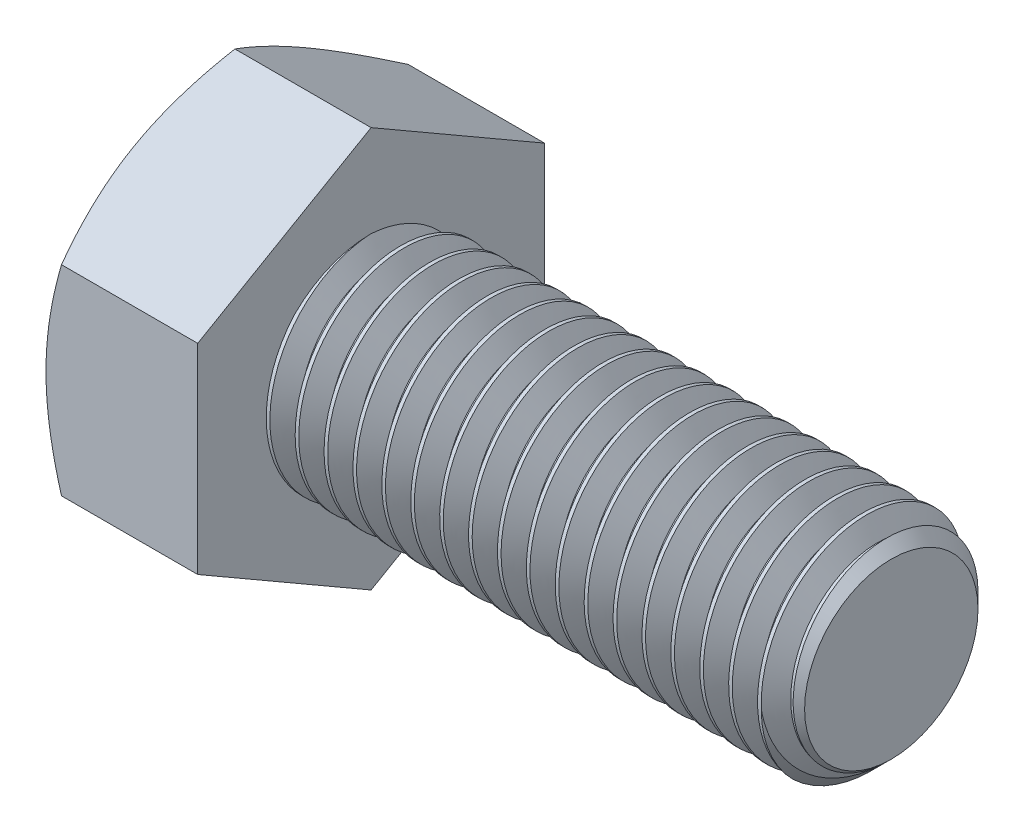
SolidWorks part; units mm, degrees
ref_plane "Front Plane" through (0, 0, 0) normal (0, 0, 1) x (1, 0, 0)
ref_plane "Top Plane" through (0, 0, 0) normal (0, 1, 0) x (1, 0, 0)
ref_plane "Right Plane" through (0, 0, 0) normal (1, 0, 0) x (0, 0, -1)
sketch "Sketch1" plane through (0, 0, 0) normal (0, 0, 1) x (1, 0, 0)
  line L0 (-12.3031, 0) -> (12.3031, 0) construction
  line L1 (12.3031, 3.9688) -> (12.3031, -3.9688) construction
  line L2 (-6.7469, 6.35) -> (-6.7469, -6.35) construction
  line L3 (-12.3031, 6.35) -> (-12.3031, -6.35) construction
  point P9 (-6.7469, 0)
  point P10 (8.599, -3.9688)
  dimension "D1" = 3.7042
  dimension "Screw Dia" = 7.9375
  dimension "Hex" = 12.7
  dimension "Head Ht" = 5.5562
  dimension "Screw Lenght" = 19.05
ref_plane "Plane2" through (12.3031, 0, 0) normal (1, 0, 0) x (0, 0, -1)
sketch "Sketch5" plane through (12.3031, 0, 0) normal (1, 0, 0) x (0, 0, -1)
  circle A0 centre (0, 0) radius 3.9688
extrude "Boss-Extrude3" add sketch "Sketch5" against normal up to vertex (19.05 mm away) up to point (-6.7469, 0, 0)
sketch "Sketch9" plane through (12.3031, 0, 0) normal (1, 0, 0) x (0, 0, -1)
  circle A1 centre (0, 0) radius 3.9688
  circle A2 centre (0, 0) radius 3.9688
  dimension "D1" = 0
curve "Helix/Spiral1" pitch 1.0583 height 20.1083 turns 19 parameters "Pitch"=1.0583
chamfer "Chamfer1" distance 0.7937 angle 45 1 edges at (12.3031, 0, -3.9688)
sketch "Sketch10" plane through (0, 0, 0) normal (0, 0, 1) x (1, 0, 0)
  line L0 (12.3031, 3.9688) -> (12.7, 3.2813)
  line L1 (12.7, 3.2813) -> (12.8323, 3.2813)
  line L2 (12.8323, 3.2813) -> (13.2292, 3.9688)
  line L3 (12.3031, 3.9688) -> (13.2292, 3.9688)
  line L4 (12.7661, 3.9688) -> (12.7661, 3.2813) construction
  line L5 (12.5016, 3.625) -> (13.0307, 3.625) construction
  dimension "D1" = 60
  dimension "D2" = 0.1323
  dimension "D3" = 0.5292
sweep "Cut-Sweep1" cut profiles "Sketch10" path "Helix/Spiral1"
sketch "Sketch6" plane through (-6.7469, 0, 0) normal (-1, 0, 0) x (0, 0, 1)
  line L0 (0, 6.35) -> (0, -6.35) construction
  line L1 (6.35, 3.6662) -> (0, 7.3323)
  line L2 (0, 7.3323) -> (-6.35, 3.6662)
  line L3 (-6.35, 3.6662) -> (-6.35, -3.6662)
  line L4 (-6.35, -3.6662) -> (0, -7.3323)
  line L5 (0, -7.3323) -> (6.35, -3.6662)
  line L6 (6.35, -3.6662) -> (6.35, 3.6662)
  circle A0 centre (0, 0) radius 6.35 construction
extrude "Boss-Extrude4" add sketch "Sketch6" along normal up to vertex (5.5563 mm away) up to point (-12.3031, -6.35, 0)
sketch "Sketch7" plane through (-12.3031, 0, 0) normal (-1, 0, 0) x (0, 0, 1)
  circle A0 centre (0, 0) radius 6.35 construction
  circle A1 centre (0, 0) radius 6.35
sketch "Sketch8" plane through (-12.3031, 0, 0) normal (-1, 0, 0) x (0, 0, 1)
  circle A0 centre (0, 0) radius 6.35 construction
  circle A1 centre (0, 0) radius 6.35
extrude "Cut-Extrude3" cut sketch "Sketch8" against normal through all draft 60 flip side to cut
sketch "Sketch12" plane through (-12.3031, 0, 0) normal (-1, 0, 0) x (0, 0, 1)
  line L0 (0, 4.8895) -> (0, 2.7305) construction
  line L1 (0.1905, 4.8895) -> (0.1905, 2.7305)
  line L2 (-0.1905, 4.8895) -> (-0.1905, 2.7305)
  line L3 (0, 3.9688) -> (0, -3.9688) construction
  arc A0 (0.1905, 4.8895) -> (-0.1905, 4.8895) centre (0, 4.8895) ccw
  arc A1 (-0.1905, 2.7305) -> (0.1905, 2.7305) centre (0, 2.7305) ccw
  circle A3 centre (0, 0) radius 2.54 construction
  circle A4 centre (0, 0) radius 5.08 construction
  point P2 (0, 3.81)
  dimension "D1" = 5.08
  dimension "D3" = 10.16
  dimension "D2" = 0.381
extrude "Cut-Extrude4" cut sketch "Sketch12" against normal blind 0.254
pattern_circular "CirPattern1" count 6 over 360 about axis through (0, 0, 0) along (1, 0, 0) of "Cut-Extrude4"
equation "\"D2@Sketch10\" = \"Pitch@Helix/Spiral1\"*.125"
equation "\"D3@Sketch10\" = \"Pitch@Helix/Spiral1\"*.5"
equation "\"D3@Helix/Spiral1\" = \"Screw Lenght@Sketch1\"+\"Pitch@Helix/Spiral1\""
equation "\"D1@Chamfer1\" = \"Pitch@Helix/Spiral1\"*.75"
equation "\"D1@Sketch12\" = \"Hex@Sketch1\"*.4"
equation "\"D3@Sketch12\" = \"Hex@Sketch1\"*.8"
equation "\"D2@Sketch12\" = \"Hex@Sketch1\"*.03"
equation "\"D1@Sketch1\" = \"Pitch@Helix/Spiral1\"*3.5"
